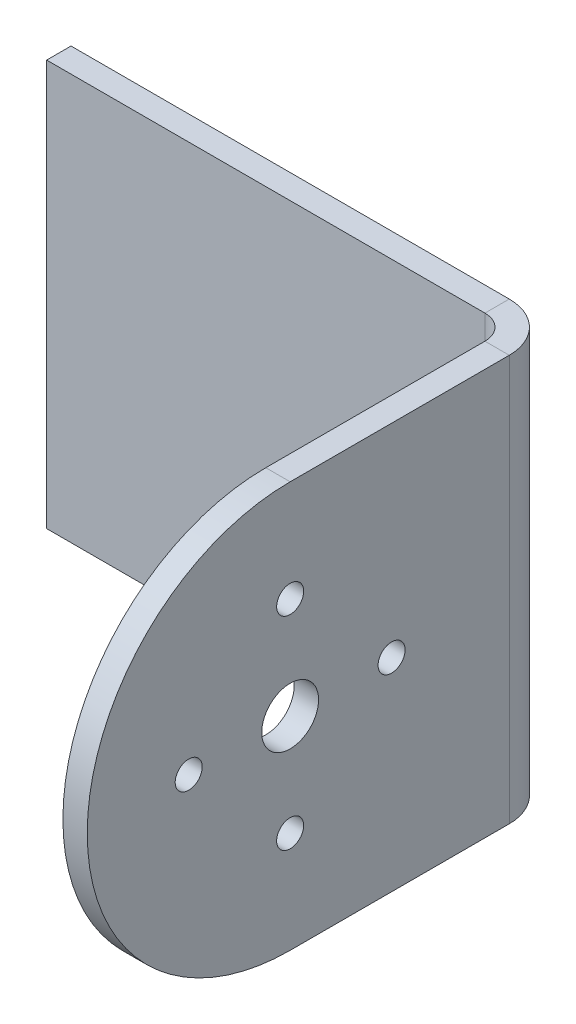
SolidWorks part; units mm, degrees
note: The reader was unsure of these and kept them because the rebuilt part matched: flange length of "Edge-Flange1".
material "Alumina"
ref_plane "Front Plane" through (0, 0, 0) normal (0, 0, 1) x (1, 0, 0)
ref_plane "Top Plane" through (0, 0, 0) normal (0, 1, 0) x (1, 0, 0)
ref_plane "Right Plane" through (0, 0, 0) normal (1, 0, 0) x (0, 0, -1)
sketch "Sketch1" plane through (0, 0, 0) normal (0, 0, 1) x (1, 0, 0)
  line L1 (30, 25) -> (-30, 25)
  line L2 (30, 25) -> (30, -25)
  line L3 (30, -25) -> (-30, -25)
  line L4 (-30, 25) -> (-30, -25)
  line L5 (30, 25) -> (-30, -25) construction
  line L6 (30, -25) -> (-30, 25) construction
  point P0 (0, 0)
  dimension "D1" = 60
  dimension "D2" = 50
base flange "Base-Flange1" sketch "Sketch1" thickness 3 reverse thickness direction no parameters "D1"=3
edge flange "Edge-Flange1" sketch "Sketch8" flange angle 90 flange length 60 flange position material inside bend radius 3 thickness 3 relief rectangular parameters "D6"=10
sketch "Sketch8" plane through (30, 0, 0) normal (1, 0, 0) x (0, 1, 0)
  line L2 (-25, 0) -> (-25, 57)
  line L3 (-25, 57) -> (25, 57)
  line L4 (25, 57) -> (25, 0)
  line L7 (-25, 0) -> (25, 0) construction
  line L8 (-25, 0) -> (25, 0)
bend "EdgeBend1" bend radius 3 bend angle 90 parameters "D5"=1
sketch "Sketch9" plane through (30, 0, 0) normal (1, 0, 0) x (0, 0, -1)
  line L0 (0, 0) -> (-57, 0) construction
  line L1 (-57, 25) -> (-57, -25) construction
  line L2 (-30, 25) -> (-30, -25) construction
  line L3 (-3, 25) -> (-57, 25) construction
  line L4 (-57, -25) -> (-3, -25) construction
  line L5 (-30, 25) -> (-57, 25)
  line L6 (-57, 25) -> (-57, -25)
  line L7 (-57, -25) -> (-30, -25)
  arc A0 (-30, 25) -> (-30, -25) centre (-30, 0) ccw
extrude "Cut-Extrude1" cut sketch "Sketch9" against normal blind 10 normal cut yes
sketch "Sketch10" plane through (30, 0, 0) normal (1, 0, 0) x (0, 0, -1)
  line L0 (0, 0) -> (-55, 0) construction
  line L1 (-30, 25) -> (-30, -25) construction
  circle A0 centre (-30, 0) radius 3.5
  arc A1 (-30, 25) -> (-30, -25) centre (-30, 0) ccw construction
  circle A2 centre (-30, 12.5) radius 1.665
  circle A3 centre (-42.5, 0) radius 1.665
  circle A4 centre (-30, -12.5) radius 1.665
  circle A5 centre (-17.5, 0) radius 1.665
  point P13 (-30, 0)
  dimension "D1" = 7
  dimension "D2" = 3.33
  dimension "D4" = 3.33
  dimension "D3" = 12.5
  dimension "D5" = 12.5
extrude "Cut-Extrude2" cut sketch "Sketch10" against normal blind 10 normal cut yes
sketch "Bend-Lines1" [suppressed] plane through (0, 0, 0) normal (0, 1, 0) x (1, 0, 0)
sketch "Bounding-Box1" [suppressed] plane through (0, 0, 0) normal (0, 1, 0) x (1, 0, 0)
sheet metal parameters "Sheet-Metal1" thickness 3 parameters "D1"=3
flat pattern "Flat-Pattern1" [suppressed]
sketch "Bend-Lines2" plane through (0, 0, 0) normal (0, 1, 0) x (1, 0, 0)
sketch3d "Bounding-Box2" [suppressed]
  line L0 (50, -25, 0) -> (-50, -25, 0) construction
  line L1 (50, 25, 0) -> (-50, 25, 0) construction
  line L2 (50, -25, 0) -> (50, 25, 0) construction
  line L3 (-50, -25, 0) -> (-50, 25, 0) construction
sheet metal parameters "Sheet-Metal2" thickness 3 parameters "D1"=3
flat pattern "Flat-Pattern1"
sketch "Bend-Lines2" plane through (0, 0, 0) normal (0, 0, 1) x (1, 0, 0)
  line L0 (27.5343, -25) -> (27.5343, 25) construction
  line L1 (27.5343, -25) -> (27.5343, 25) construction
sketch3d "Bounding-Box2" [suppressed]
  line L0 (-30, -25, 0) -> (85.0686, -25, 0) construction
  line L1 (-30, 25, 0) -> (85.0686, 25, 0) construction
  line L2 (-30, -25, 0) -> (-30, 25, 0) construction
  line L3 (85.0686, -25, 0) -> (85.0686, 25, 0) construction
bend of the flat pattern "Flatten-<EdgeBend1>1"
sheet metal parameters "Sheet-Metal3" thickness 3 parameters "D1"=3
flat pattern "Flat-Pattern1"
sketch "Bend-Lines2" plane through (0, 0, 0) normal (0, 0, 1) x (1, 0, 0)
  line L0 (27.5343, -25) -> (27.5343, 25) construction
  line L1 (27.5343, -25) -> (27.5343, 25) construction
sketch3d "Bounding-Box2" [suppressed]
  line L0 (-30, 25, 0) -> (83.0686, 25, 0) construction
  line L1 (-30, -25, 0) -> (83.0686, -25, 0) construction
  line L2 (-30, 25, 0) -> (-30, -25, 0) construction
  line L3 (83.0686, 25, 0) -> (83.0686, -25, 0) construction
bend of the flat pattern "Flatten-<EdgeBend1>1"
sheet metal parameters "Sheet-Metal4" thickness 3 parameters "D1"=3
flat pattern "Flat-Pattern1"
sketch "Bend-Lines2" plane through (0, 0, 0) normal (0, 0, 1) x (1, 0, 0)
  line L0 (27.5343, -25) -> (27.5343, 25) construction
  line L1 (27.5343, -25) -> (27.5343, 25) construction
sketch3d "Bounding-Box2" [suppressed]
  line L0 (-30, 25, 0) -> (83.0686, 25, 0) construction
  line L1 (-30, -25, 0) -> (83.0686, -25, 0) construction
  line L2 (-30, 25, 0) -> (-30, -25, 0) construction
  line L3 (83.0686, 25, 0) -> (83.0686, -25, 0) construction
bend of the flat pattern "Flatten-<EdgeBend1>1"
